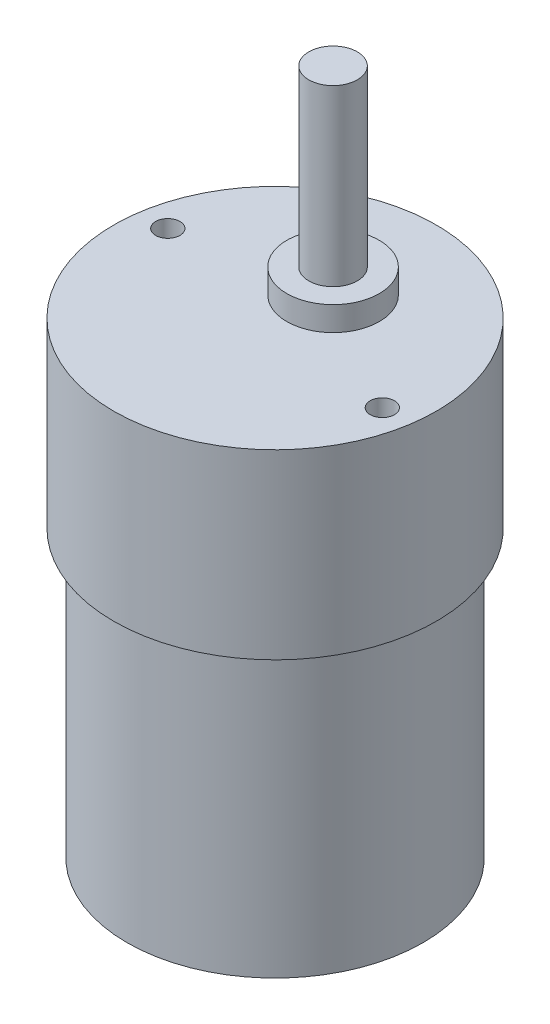
SolidWorks part; units mm, degrees
ref_plane "Front Plane" through (0, 0, 0) normal (0, 0, 1) x (1, 0, 0)
ref_plane "Top Plane" through (0, 0, 0) normal (0, 1, 0) x (1, 0, 0)
ref_plane "Right Plane" through (0, 0, 0) normal (1, 0, 0) x (0, 0, -1)
sketch "Sketch1" plane through (0, 0, 0) normal (0, 1, 0) x (1, 0, 0)
  circle A0 centre (0, 0) radius 13.3
  dimension "D1" = 26.6
extrude "Boss-Extrude1" add sketch "Sketch1" along normal blind 15
sketch "Sketch2" plane through (0, 0, 0) normal (0, -1, 0) x (1, 0, 0)
  circle A0 centre (0, 0) radius 12.2
  dimension "D1" = 24.4
extrude "Boss-Extrude2" add sketch "Sketch2" along normal blind 23.5
sketch "Sketch3" plane through (0, 15, 0) normal (0, 1, 0) x (1, 0, 0)
  circle A1 centre (10.8208, -1.9776) radius 1
  circle A2 centre (-10.8208, 1.9776) radius 1
  circle A3 centre (0.7389, 4.043) radius 3.81
  circle A6 centre (0, 0) radius 13.3 construction
  point P12 (0.0539, 0.2951)
  dimension "D1" = 10.8208
  dimension "D2" = 2
  dimension "D3" = 2
  dimension "D4" = 7.62
  dimension "D5" = 0.7389
  dimension "D7" = 4.043
  dimension "D6" = 10.8208
  dimension "D8" = 1.9776
  dimension "D9" = 1.9776
extrude "Boss-Extrude4" add sketch "Sketch3" along normal blind 2 contours A3
extrude "Cut-Extrude2" cut sketch "Sketch3<6>" against normal blind 4
sketch "Sketch3<6>" plane through (0, 15, 0) normal (0, 1, 0) x (1, 0, 0) same geometry as "Sketch3"
sketch "Sketch7" plane through (0, 17, 0) normal (0, 1, 0) x (1, 0, 0)
  circle A0 centre (0.7389, 4.043) radius 2
  dimension "D1" = 4
extrude "Boss-Extrude5" add sketch "Sketch7" along normal blind 14.36
